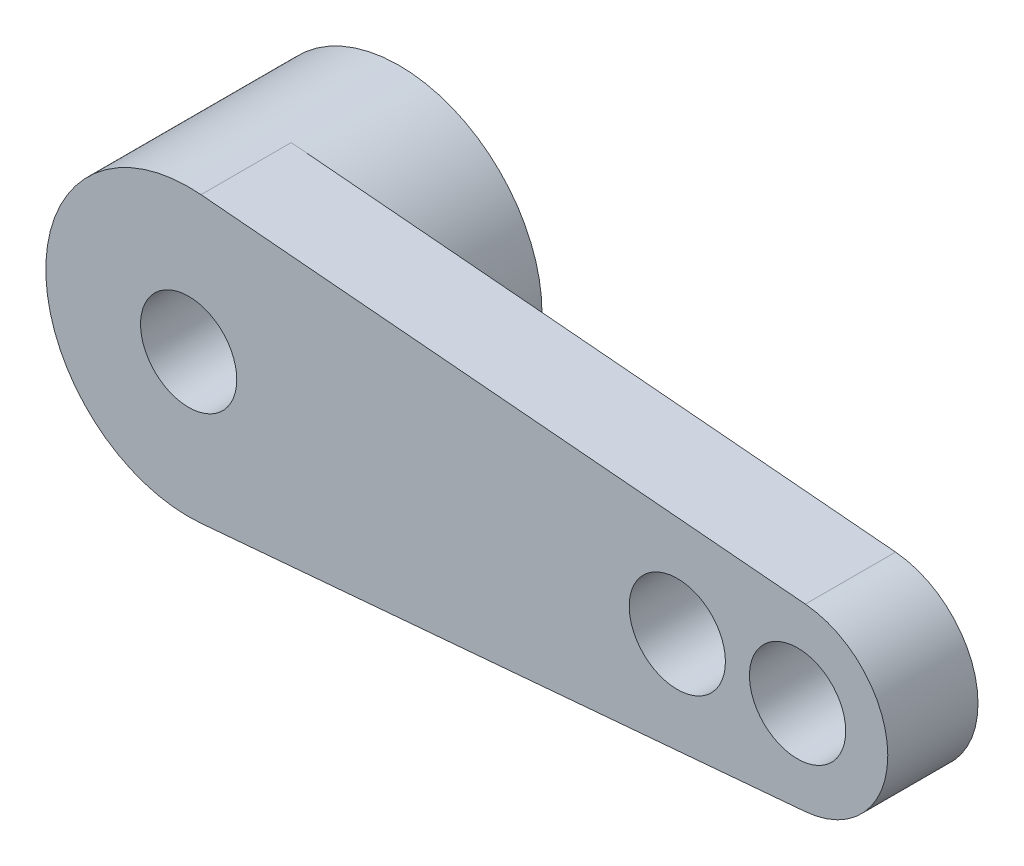
SolidWorks part; units mm, degrees
ref_plane "Front Plane" through (0, 0, 0) normal (0, 0, 1) x (1, 0, 0)
ref_plane "Top Plane" through (0, 0, 0) normal (0, 1, 0) x (1, 0, 0)
ref_plane "Right Plane" through (0, 0, 0) normal (1, 0, 0) x (0, 0, -1)
sketch "Sketch1" plane through (0, 0, 0) normal (0, 0, 1) x (1, 0, 0)
  line L0 (0.4105, 4.7322) -> (20.5093, 2.9888)
  line L1 (20.5093, -2.9888) -> (0.4105, -4.7322)
  circle A0 centre (0, 0) radius 2.5
  circle A1 centre (0, 0) radius 4.75
  circle A2 centre (16.25, 0) radius 1.6
  circle A3 centre (20.25, 0) radius 1.6
  circle A4 centre (20.25, 0) radius 3
  point P9 (-4.75, 0)
  point P10 (23.25, 0)
  dimension "D1" = 5
  dimension "D2" = 9.5
  dimension "D3" = 3.2
  dimension "D4" = 3.2
  dimension "D5" = 6
  dimension "D6" = 28
  dimension "D7" = 16.25
extrude "Boss-Extrude1" add sketch "Sketch1" along normal blind 3 contours A1 A0 | A4 L0 A1 L1 A2 | A4 A2 A3 region at (10.1196, 0, 0) region at (3.4019, 3.1195, 0) region at (22.3996, 1.9712, 0)
extrude "Boss-Extrude2" add sketch "Sketch1<3>" against normal blind 4 contours A1 A0 region at (3.4019, 3.1195, 0)
sketch "Sketch1<3>" plane through (0, 0, 0) normal (0, 0, 1) x (1, 0, 0) same geometry as "Sketch1"
sketch "Sketch2" plane through (0, 0, -4) normal (0, 0, -1) x (-1, 0, 0)
  line L0 (0, 0) -> (0, 3.2459) construction
  line L1 (0, 0) -> (0.3768, 3.2239) construction
  line L2 (-20.5093, -2.9888) -> (-0.4105, -4.7322)
  line L3 (-0.4105, 4.7322) -> (-20.5093, 2.9888)
  line L4 (-20.5093, -2.9888) -> (-0.4105, -4.7322)
  line L5 (-0.4105, 4.7322) -> (-20.5093, 2.9888)
  line L6 (0, 0) -> (0.7485, 3.1584) construction
  line L7 (0, 0) -> (1.1101, 3.0501) construction
  line L8 (0, 0) -> (1.4567, 2.9006) construction
  line L9 (0, 0) -> (1.7836, 2.7119) construction
  line L10 (0, 0) -> (2.0864, 2.4865) construction
  line L11 (0, 0) -> (2.3609, 2.2274) construction
  line L12 (0, 0) -> (2.6036, 1.9383) construction
  line L13 (0, 0) -> (2.811, 1.6229) construction
  line L14 (0, 0) -> (2.9804, 1.2856) construction
  line L15 (0, 0) -> (3.1095, 0.9309) construction
  line L16 (0, 0) -> (3.1965, 0.5636) construction
  line L17 (0, 0) -> (3.2404, 0.1887) construction
  line L18 (0, 0) -> (3.2404, -0.1887) construction
  line L19 (0, 0) -> (3.1965, -0.5636) construction
  line L20 (0, 0) -> (3.1095, -0.9309) construction
  line L21 (0, 0) -> (2.9804, -1.2856) construction
  line L22 (0, 0) -> (2.811, -1.6229) construction
  line L23 (0, 0) -> (2.6036, -1.9383) construction
  line L24 (0, 0) -> (2.3609, -2.2274) construction
  line L25 (0, 0) -> (2.0864, -2.4865) construction
  line L26 (0, 0) -> (1.7836, -2.7119) construction
  line L27 (0, 0) -> (1.4567, -2.9006) construction
  line L28 (0, 0) -> (1.1101, -3.0501) construction
  line L29 (0, 0) -> (0.7485, -3.1584) construction
  line L30 (0, 0) -> (0.3768, -3.2239) construction
  line L31 (0, 0) -> (0, -3.2459) construction
  line L32 (0, 0) -> (-0.3768, -3.2239) construction
  line L33 (0, 0) -> (-0.7485, -3.1584) construction
  line L34 (0, 0) -> (-1.1101, -3.0501) construction
  line L35 (0, 0) -> (-1.4567, -2.9006) construction
  line L36 (0, 0) -> (-1.7836, -2.7119) construction
  line L37 (0, 0) -> (-2.0864, -2.4865) construction
  line L38 (0, 0) -> (-2.3609, -2.2274) construction
  line L39 (0, 0) -> (-2.6036, -1.9383) construction
  line L40 (0, 0) -> (-2.811, -1.6229) construction
  line L41 (0, 0) -> (-2.9804, -1.2856) construction
  line L42 (0, 0) -> (-3.1095, -0.9309) construction
  line L43 (0, 0) -> (-3.1965, -0.5636) construction
  line L44 (0, 0) -> (-3.2404, -0.1887) construction
  line L45 (0, 0) -> (-3.2404, 0.1887) construction
  line L46 (0, 0) -> (-3.1965, 0.5636) construction
  line L47 (0, 0) -> (-3.1095, 0.9309) construction
  line L48 (0, 0) -> (-2.9804, 1.2856) construction
  line L49 (0, 0) -> (-2.811, 1.6229) construction
  line L50 (0, 0) -> (-2.6036, 1.9383) construction
  line L51 (0, 0) -> (-2.3609, 2.2274) construction
  line L52 (0, 0) -> (-2.0864, 2.4865) construction
  line L53 (0, 0) -> (-1.7836, 2.7119) construction
  line L54 (0, 0) -> (-1.4567, 2.9006) construction
  line L55 (0, 0) -> (-1.1101, 3.0501) construction
  line L56 (0, 0) -> (-0.7485, 3.1584) construction
  line L57 (0, 0) -> (-0.3768, 3.2239) construction
  line L58 (-0.1333, 3) -> (-0.2902, 2.4831)
  line L59 (0.1333, 3) -> (0.2902, 2.4831)
  line L60 (-0.1333, 3) -> (0.1333, 3)
  line L61 (0.5621, 2.9499) -> (0.2902, 2.4831)
  line L62 (0.5621, 2.9499) -> (0.8216, 2.8884)
  line L63 (0.8216, 2.8884) -> (0.8551, 2.3492)
  line L64 (1.2272, 2.7407) -> (0.8551, 2.3492)
  line L65 (1.2272, 2.7407) -> (1.4656, 2.6211)
  line L66 (1.4656, 2.6211) -> (1.3738, 2.0887)
  line L67 (1.8262, 2.3838) -> (1.3738, 2.0887)
  line L68 (1.8262, 2.3838) -> (2.0305, 2.2124)
  line L69 (2.0305, 2.2124) -> (1.8184, 1.7156)
  line L70 (2.3267, 1.8984) -> (1.8184, 1.7156)
  line L71 (2.3267, 1.8984) -> (2.486, 1.6845)
  line L72 (2.486, 1.6845) -> (2.1651, 1.25)
  line L73 (2.7018, 1.3107) -> (2.1651, 1.25)
  line L74 (2.7018, 1.3107) -> (2.8075, 1.0658)
  line L75 (2.8075, 1.0658) -> (2.395, 0.717)
  line L76 (2.9313, 0.6523) -> (2.395, 0.717)
  line L77 (2.9313, 0.6523) -> (2.9776, 0.3896)
  line L78 (2.9776, 0.3896) -> (2.4958, 0.1454)
  line L79 (3.0027, -0.0413) -> (2.4958, 0.1454)
  line L80 (3.0027, -0.0413) -> (2.9872, -0.3075)
  line L81 (2.9872, -0.3075) -> (2.462, -0.4341)
  line L82 (2.9122, -0.7327) -> (2.462, -0.4341)
  line L83 (2.9122, -0.7327) -> (2.8357, -0.9881)
  line L84 (2.8357, -0.9881) -> (2.2955, -0.9902)
  line L85 (2.6647, -1.3845) -> (2.2955, -0.9902)
  line L86 (2.6647, -1.3845) -> (2.5314, -1.6155)
  line L87 (2.5314, -1.6155) -> (2.0053, -1.4929)
  line L88 (2.2736, -1.9617) -> (2.0053, -1.4929)
  line L89 (2.2736, -1.9617) -> (2.0906, -2.1557)
  line L90 (2.0906, -2.1557) -> (1.607, -1.9151)
  line L91 (1.7599, -2.4332) -> (1.607, -1.9151)
  line L92 (1.7599, -2.4332) -> (1.5371, -2.5797)
  line L93 (1.5371, -2.5797) -> (1.122, -2.2341)
  line L94 (1.1514, -2.7735) -> (1.122, -2.2341)
  line L95 (1.1514, -2.7735) -> (0.9008, -2.8647)
  line L96 (0.9008, -2.8647) -> (0.5765, -2.4326)
  line L97 (0.4807, -2.9642) -> (0.5765, -2.4326)
  line L98 (0.4807, -2.9642) -> (0.2158, -2.9952)
  line L99 (0.2158, -2.9952) -> (0, -2.5)
  line L100 (-0.2158, -2.9952) -> (0, -2.5)
  line L101 (-0.2158, -2.9952) -> (-0.4807, -2.9642)
  line L102 (-0.4807, -2.9642) -> (-0.5765, -2.4326)
  line L103 (-0.9008, -2.8647) -> (-0.5765, -2.4326)
  line L104 (-0.9008, -2.8647) -> (-1.1514, -2.7735)
  line L105 (-1.1514, -2.7735) -> (-1.122, -2.2341)
  line L106 (-1.5371, -2.5797) -> (-1.122, -2.2341)
  line L107 (-1.5371, -2.5797) -> (-1.7599, -2.4332)
  line L108 (-1.7599, -2.4332) -> (-1.607, -1.9151)
  line L109 (-2.0906, -2.1557) -> (-1.607, -1.9151)
  line L110 (-2.0906, -2.1557) -> (-2.2736, -1.9617)
  line L111 (-2.2736, -1.9617) -> (-2.0053, -1.4929)
  line L112 (-2.5314, -1.6155) -> (-2.0053, -1.4929)
  line L113 (-2.5314, -1.6155) -> (-2.6647, -1.3845)
  line L114 (-2.6647, -1.3845) -> (-2.2955, -0.9902)
  line L115 (-2.8357, -0.9881) -> (-2.2955, -0.9902)
  line L116 (-2.8357, -0.9881) -> (-2.9122, -0.7327)
  line L117 (-2.9122, -0.7327) -> (-2.462, -0.4341)
  line L118 (-2.9872, -0.3075) -> (-2.462, -0.4341)
  line L119 (-2.9872, -0.3075) -> (-3.0027, -0.0413)
  line L120 (-3.0027, -0.0413) -> (-2.4958, 0.1454)
  line L121 (-2.9776, 0.3896) -> (-2.4958, 0.1454)
  line L122 (-2.9776, 0.3896) -> (-2.9313, 0.6523)
  line L123 (-2.9313, 0.6523) -> (-2.395, 0.717)
  line L124 (-2.8075, 1.0658) -> (-2.395, 0.717)
  line L125 (-2.8075, 1.0658) -> (-2.7018, 1.3107)
  line L126 (-2.7018, 1.3107) -> (-2.1651, 1.25)
  line L127 (-2.486, 1.6845) -> (-2.1651, 1.25)
  line L128 (-2.486, 1.6845) -> (-2.3267, 1.8984)
  line L129 (-2.3267, 1.8984) -> (-1.8184, 1.7156)
  line L130 (-2.0305, 2.2124) -> (-1.8184, 1.7156)
  line L131 (-2.0305, 2.2124) -> (-1.8262, 2.3838)
  line L132 (-1.8262, 2.3838) -> (-1.3738, 2.0887)
  line L133 (-1.4656, 2.6211) -> (-1.3738, 2.0887)
  line L134 (-1.4656, 2.6211) -> (-1.2272, 2.7407)
  line L135 (-1.2272, 2.7407) -> (-0.8551, 2.3492)
  line L136 (-0.8216, 2.8884) -> (-0.8551, 2.3492)
  line L137 (-0.8216, 2.8884) -> (-0.5621, 2.9499)
  line L138 (-0.5621, 2.9499) -> (-0.2902, 2.4831)
  circle A1 centre (0, 0) radius 2.5
  arc A2 (-0.4105, 4.7322) -> (-0.4105, -4.7322) centre (0, 0) ccw
  arc A3 (-20.5093, 2.9888) -> (-20.5093, -2.9888) centre (-20.25, 0) ccw
  arc A4 (-0.4105, 4.7322) -> (-0.4105, -4.7322) centre (0, 0) ccw
  arc A5 (-20.5093, 2.9888) -> (-20.5093, -2.9888) centre (-20.25, 0) ccw
  circle A6 centre (0, 0) radius 2.5
  point P11 (-0.0762, 3.2837)
  point P65 (0, 0)
  point P69 (0.1944, 3.2837)
  point P70 (0.166, 3.1099)
  point P71 (0, 3)
  dimension "D5" = 3
  dimension "D3" = 54
  dimension "D4" = 27
  dimension "D1" = 0
  dimension "D2" = 0
extrude "Cut-Extrude1" cut sketch "Sketch2" against normal blind 4 contours L117 L118 L119 L120 L121 L122 L123 L124 L125 L126 L127 L128 L129 L130 L131 L132 L133 L134 L135 L136 L137 L138 L58 L60 L59 L61 L62 L63 L64 L65 L66 L67 L68 L69 L70 L71 L72 L73 L74 L75 L76 L77 L78 L79 L80 L81 L82 L83 L84 L85 L86 L87 L88 L89 L90 L91 L92 L93 L94 L95 L96 L97 L98 L99 L100 L101 L102 L103 L104 L105 L106 L107 L108 L109 L110 L111 L112 L113 L114 L115 L116
sketch "Sketch3" plane through (0, 0, 3) normal (0, 0, 1) x (1, 0, 0)
  circle A0 centre (0, 0) radius 2.5
  circle A1 centre (16.25, 0) radius 1.6
  circle A2 centre (16.25, 0) radius 1.6
  circle A3 centre (0, 0) radius 2.5
  circle A4 centre (0, 0) radius 2.5
  circle A5 centre (20.25, 0) radius 1.6
  circle A6 centre (20.25, 0) radius 1.6
  circle A7 centre (0, 0) radius 1.6
  circle M6 centre (0, 0) radius 2.5
  dimension "D4" = 3.2
  dimension "D1" = 0
  dimension "D2" = 0
  dimension "D3" = 0
extrude "Boss-Extrude3" add sketch "Sketch3" against normal up to surface (3 mm away) contours A7 M6 region at (-2.4293, 0, 3) up to face at (-1.9972, -1.8843, 0)
